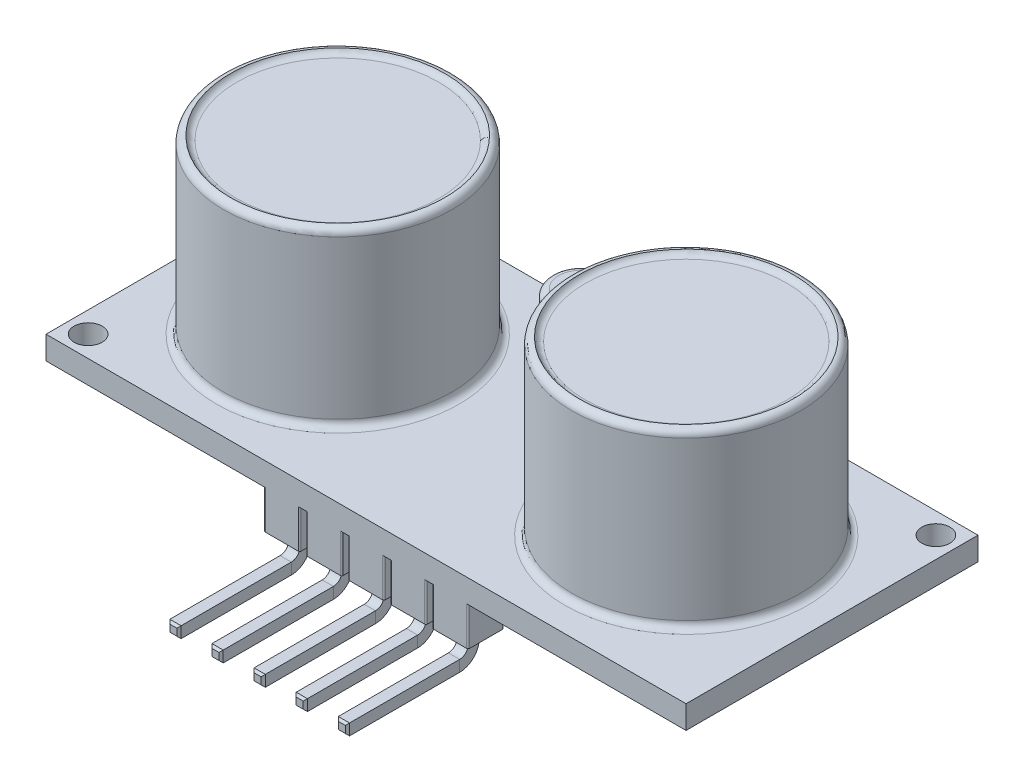
SolidWorks part; units mm, degrees
ref_plane "Front Plane" through (0, 0, 0) normal (0, 0, 1) x (1, 0, 0)
ref_plane "Top Plane" through (0, 0, 0) normal (0, 1, 0) x (1, 0, 0)
ref_plane "Right Plane" through (0, 0, 0) normal (1, 0, 0) x (0, 0, -1)
sketch "Sketch1" plane through (0, 0, 0) normal (0, 1, 0) x (1, 0, 0)
  line L1 (-22.8, -10.4) -> (22.8, -10.4)
  line L2 (-22.8, -10.4) -> (-22.8, 10.4)
  line L3 (-22.8, 10.4) -> (22.8, 10.4)
  line L4 (22.8, -10.4) -> (22.8, 10.4)
  line L5 (-22.8, -10.4) -> (22.8, 10.4) construction
  line L6 (-22.8, 10.4) -> (22.8, -10.4) construction
  point P0 (0, 0)
  dimension "D1" = 45.6
  dimension "D2" = 20.8
extrude "Boss-Extrude1" add sketch "Sketch1" along normal blind 1.65
sketch "Sketch2" plane through (0, 1.65, 0) normal (0, 1, 0) x (1, 0, 0)
  line L0 (-3.175, 8.125) -> (3.175, 8.125) construction
  line L1 (-3.175, 10.25) -> (3.175, 10.25)
  line L2 (-3.175, 6) -> (3.175, 6)
  line L3 (22.8, 10.4) -> (-22.8, 10.4) construction
  arc A0 (-3.175, 10.25) -> (-3.175, 6) centre (-3.175, 8.125) ccw
  arc A1 (3.175, 6) -> (3.175, 10.25) centre (3.175, 8.125) ccw
  point P2 (0, 8.125)
  dimension "D1" = 6.35
  dimension "D2" = 2.125
  dimension "D3" = 0.15
extrude "Boss-Extrude2" add sketch "Sketch2" along normal blind 3.35
fillet "Fillet1" radius 0.5 4 edges at (0, 5, -6) (-5.3, 5, -8.125) (0, 5, -10.25) (5.3, 5, -8.125)
sketch "Sketch4" plane through (0, 1.65, 0) normal (0, 1, 0) x (1, 0, 0)
  line L0 (0, -10.2575) -> (0, 10.2575) construction
  circle A0 centre (12.416, 0) radius 8.15
  circle A1 centre (-12.416, 0) radius 8.15
  dimension "D1" = 16.3
extrude "Boss-Extrude3" add sketch "Sketch4" along normal blind 12.25
fillet "Fillet2" radius 0.5 4 edges at (-12.416, 1.65, -8.15) (-12.416, 13.9, -8.15) (12.416, 13.9, 8.15) (12.416, 1.65, -8.15)
sketch "Sketch6" plane through (0, 13.9, 0) normal (0, 1, 0) x (1, 0, 0)
  circle A0 centre (12.416, 0) radius 7.65 construction
  circle A1 centre (-12.416, 0) radius 7.65 construction
  circle A2 centre (12.416, 0) radius 7.65
  circle A3 centre (-12.416, 0) radius 7.65
extrude "Cut-Extrude1" cut sketch "Sketch6" against normal blind 0.3
fillet "Fillet3" radius 0.5 2 edges at (12.416, 13.6, 7.65) (-12.416, 13.6, 7.65)
sketch "Sketch7" plane through (0, 1.65, 0) normal (0, 1, 0) x (1, 0, 0)
  line L0 (22.8, -10.4) -> (22.8, 10.4) construction
  line L1 (22.8, 10.4) -> (-22.8, 10.4) construction
  line L2 (-22.8, 10.4) -> (-22.8, -10.4) construction
  line L4 (-22.8, -10.4) -> (22.8, -10.4) construction
  circle A0 centre (-21.3, -8.9) radius 1
  circle A1 centre (21.3, 8.9) radius 1
  dimension "D1" = 2
  dimension "D2" = 2
  dimension "D3" = 1.5
  dimension "D4" = 1.5
  dimension "D5" = 1.5
  dimension "D6" = 1.5
extrude "Cut-Extrude2" cut sketch "Sketch7" against normal through all
sketch "Sketch8" plane through (0, 0, 0) normal (1, 0, 0) x (0, 0, -1)
  line L0 (-9.125, 0) -> (-9.125, -3.35)
  line L1 (10.4, 0) -> (-10.4, 0) construction
  line L2 (-10.125, -4.35) -> (-18.125, -4.35)
  arc A0 (-9.125, -3.35) -> (-10.125, -4.35) centre (-10.125, -3.35) cw
  point P7 (-9.125, -4.35)
  point P8 (-10.4, 0)
  dimension "D3" = 1
  dimension "D1" = 4.35
  dimension "D2" = 9
  dimension "D4" = 1.275
sketch "Sketch9" plane through (0, 0, 0) normal (0, -1, 0) x (1, 0, 0)
  line L1 (0.4, 9.525) -> (-0.4, 9.525)
  line L2 (0.4, 9.525) -> (0.4, 8.725)
  line L3 (0.4, 8.725) -> (-0.4, 8.725)
  line L4 (-0.4, 9.525) -> (-0.4, 8.725)
  line L5 (0.4, 9.525) -> (-0.4, 8.725) construction
  line L6 (0.4, 8.725) -> (-0.4, 9.525) construction
  point P0 (0, 9.125)
  dimension "D1" = 0.8
  dimension "D2" = 0.8
sweep "Sweep1" add profiles "Sketch9" path "Sketch8"
chamfer "Chamfer1" distance 0.15 angle 45 4 edges at (0, -3.95, 18.125) (0.4, -4.35, 18.125) (0, -4.75, 18.125) (-0.4, -4.35, 18.125)
pattern_linear "LPattern3" count 3 spacing 3 along (-1, 0, 0) of "Chamfer1", "Sweep1"
pattern_linear "LPattern4" count 3 spacing 3 along (1, 0, 0) of "Chamfer1", "Sweep1"
sketch "Sketch10" plane through (0, 0, 0) normal (0, -1, 0) x (1, 0, 0)
  line L3 (-5.6, 9.525) -> (-6.4, 9.525) construction
  line L4 (-6, 9.525) -> (-6, 8.3146) construction
  line L5 (-6.4, 9.125) -> (-5.4128, 9.125) construction
  line L6 (-6.4, 9.525) -> (-6.4, 8.725) construction
  line L8 (-4.725, 10.4) -> (-7.275, 10.4)
  line L9 (-4.725, 10.4) -> (-4.725, 7.85)
  line L10 (-4.725, 7.85) -> (-7.275, 7.85)
  line L11 (-7.275, 10.4) -> (-7.275, 7.85)
  line L12 (-4.725, 10.4) -> (-7.275, 7.85) construction
  line L13 (-4.725, 7.85) -> (-7.275, 10.4) construction
  point P4 (-6, 9.125)
  dimension "D1" = 2.55
  dimension "D2" = 2.55
extrude "Boss-Extrude4" add sketch "Sketch10" along normal blind 2.75
fillet "Fillet4" radius 0.1 4 edges at (-4.725, -1.375, 10.4) (-7.275, -1.375, 10.4) (-4.725, -1.375, 7.85) (-7.275, -1.375, 7.85)
pattern_linear "LPattern5" count 5 spacing 3 along (1, 0, 0) of "Fillet4", "Boss-Extrude4"
